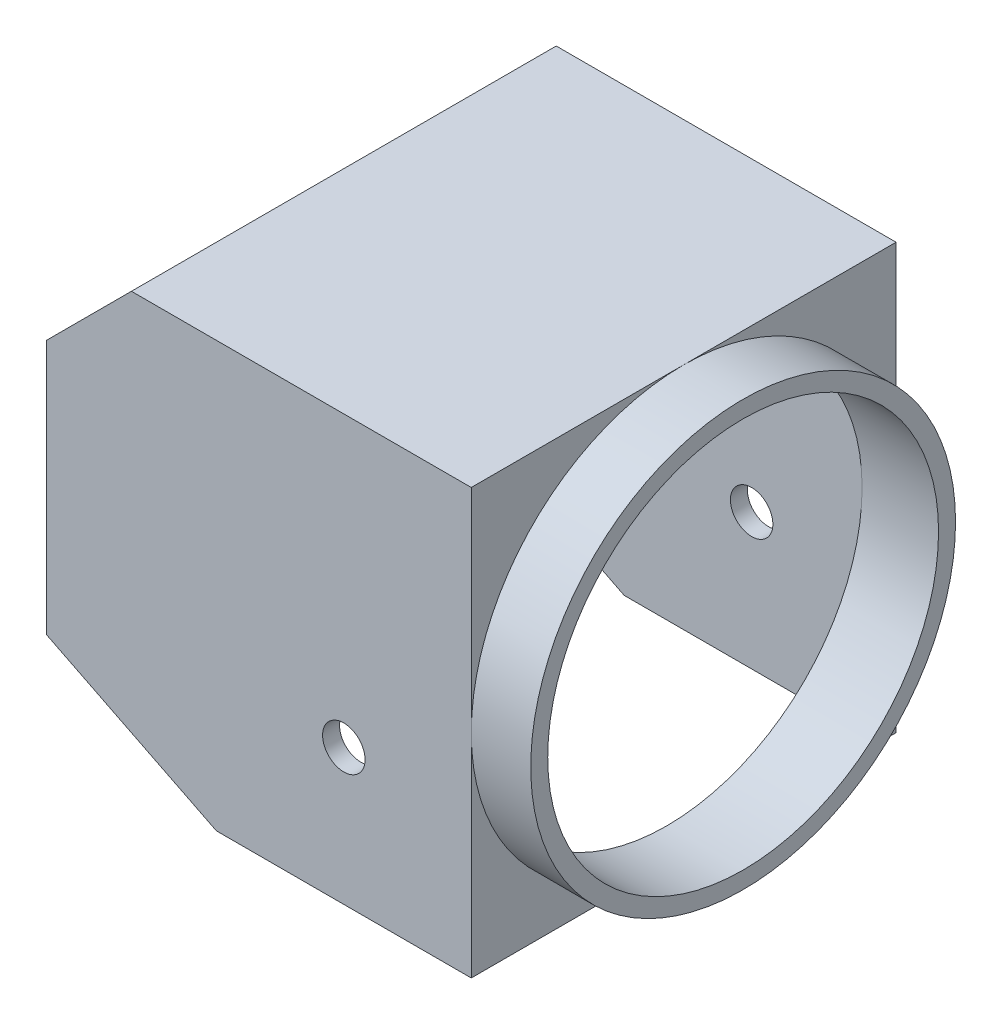
SolidWorks part; units mm, degrees
ref_plane "Plan de face" through (0, 0, 0) normal (0, 0, 1) x (1, 0, 0)
ref_plane "Plan de dessus" through (0, 0, 0) normal (0, 1, 0) x (1, 0, 0)
ref_plane "Plan de droite" through (0, 0, 0) normal (1, 0, 0) x (0, 0, -1)
sketch "Esquisse1" plane through (0, 0, 0) normal (0, 0, 1) x (1, 0, 0)
  line L0 (0, 0) -> (-30, 0)
  line L1 (-30, 0) -> (-50, 10)
  line L2 (-50, 10) -> (-50, 40)
  line L3 (-50, 40) -> (-40, 50)
  line L4 (-40, 50) -> (0, 50)
  line L5 (0, 50) -> (0, 0)
  dimension "D1" = 50
  dimension "D2" = 50
  dimension "D3" = 30
  dimension "D4" = 40
  dimension "D5" = 10
  dimension "D6" = 30
extrude "Boss.-Extru.1" add sketch "Esquisse1" along normal blind 50
sketch "Esquisse3" plane through (0, 0, 0) normal (1, 0, 0) x (0, 0, -1)
  circle A1 centre (-25, 25) radius 25
extrude "Boss.-Extru.2" add sketch "Esquisse3" along normal blind 7
sketch "Esquisse4" plane through (0, 0, 50) normal (0, 0, 1) x (1, 0, 0)
  line L0 (-50, 40) -> (-50, 10) construction
  line L2 (-30, 0) -> (0, 0) construction
  circle A0 centre (-15, 16) radius 2.5
  dimension "D1" = 5
  dimension "D2" = 35
  dimension "D3" = 16
extrude "Enlèv. mat.-Extru.1" cut sketch "Esquisse4" against normal through all
shell "Coque1" thickness 2 removed face at (-40, 5, 25) removed face at (-12, 0, 25) removed face at (7, 25, 0) removed face at (-12.5, 16, 0)
